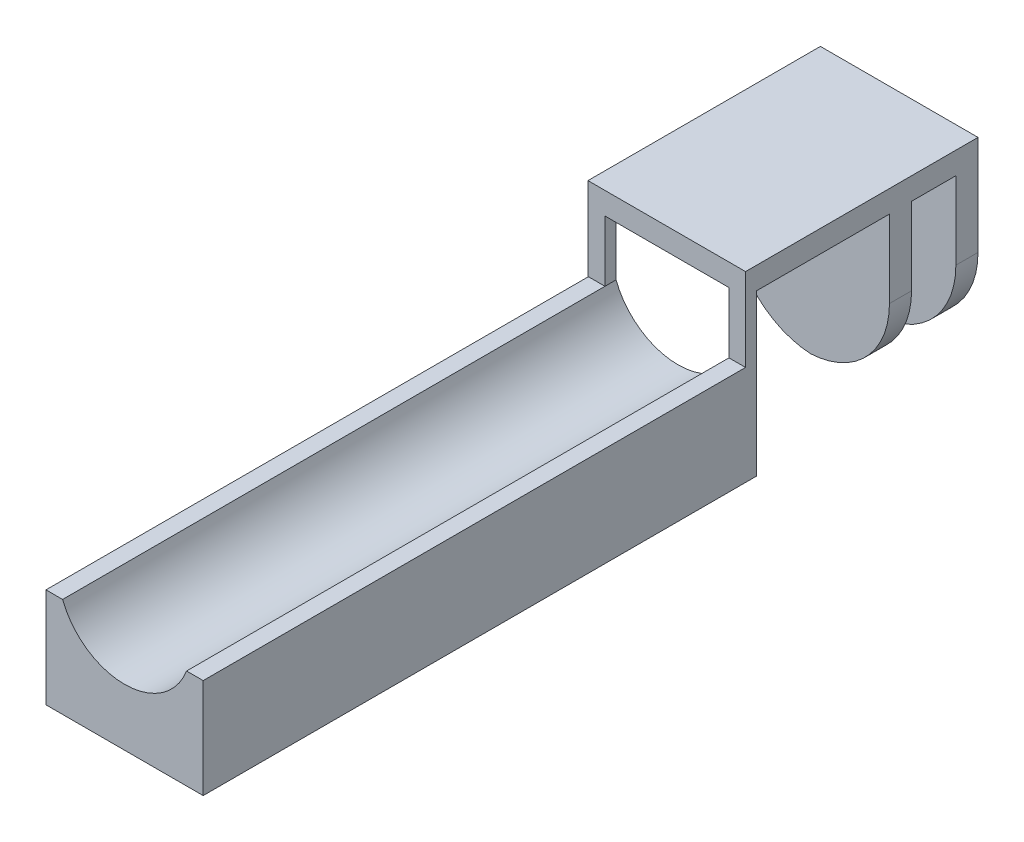
SolidWorks part; units mm, degrees
ref_plane "Front Plane" through (0, 0, 0) normal (0, 0, 1) x (1, 0, 0)
ref_plane "Top Plane" through (0, 0, 0) normal (0, 1, 0) x (1, 0, 0)
ref_plane "Right Plane" through (0, 0, 0) normal (1, 0, 0) x (0, 0, -1)
sketch "Sketch1" plane through (0, 0, 0) normal (0, 0, 1) x (1, 0, 0)
  line L0 (-223.9969, 0) -> (-253.9969, 0)
  line L1 (-253.9969, 0) -> (-253.9969, -180)
  line L2 (-253.9969, -180) -> (30, -180)
  line L3 (30, -180) -> (30, 0)
  line L4 (30, 0) -> (0, 0)
  line L5 (-111.9984, -180) -> (-111.9984, -67.8833) construction
  arc A0 (0, 0) -> (-223.9969, 0) centre (-111.9984, 43.0854) cw
  dimension "D1" = 120
  dimension "D2" = 30
  dimension "D3" = 180
extrude "Boss-Extrude1" add sketch "Sketch1" along normal blind 1000
sketch "Sketch2" plane through (0, 0, 0) normal (0, 0, -1) x (-1, 0, 0)
  line L1 (-30, 0) -> (0, 0)
  line L2 (-30, 0) -> (-30, 150)
  line L3 (-30, 150) -> (0, 150)
  line L4 (0, 0) -> (0, 110)
  line L5 (223.9969, 0) -> (254.7678, 0)
  line L6 (223.9969, 0) -> (223.9969, 110)
  line L7 (223.9969, 150) -> (254.7678, 150)
  line L8 (254.7678, 0) -> (254.7678, 150)
  line L9 (-30, 150) -> (254.7678, 150)
  line L10 (-30, 150) -> (-30, 110)
  line L11 (0, 110) -> (223.9969, 110)
  line L12 (254.7678, 150) -> (254.7678, 110)
  line M5 (0, 0) -> (-30, 0)
  line M9 (253.9969, 0) -> (223.9969, 0)
  dimension "D1" = 150
  dimension "D2" = 40
extrude "Boss-Extrude2" add sketch "Sketch2" against normal blind 20 contours L4 L11 L6 L5 L8 L7 L9 L3 L2 M9 M5 region at (26.7814, 55, 0)
sketch "Sketch3" plane through (0, 0, 0) normal (0, 0, -1) x (-1, 0, 0)
  line L0 (254.7678, 0) -> (254.7678, 150) construction
  line L1 (-30, 150) -> (254.7678, 150)
  line L2 (-30, 150) -> (-30, 110)
  line L3 (-30, 110) -> (254.7678, 110)
  line L4 (254.7678, 150) -> (254.7678, 110)
  dimension "D1" = 40
extrude "Boss-Extrude4" add sketch "Sketch3" along normal blind 400
sketch "Sketch4" plane through (0, 110, 0) normal (0, -1, 0) x (1, 0, 0)
  line L0 (30, -400) -> (30, 0) construction
  line L1 (-254.7678, -400) -> (30, -400)
  line L2 (-254.7678, -400) -> (-254.7678, -360)
  line L3 (-254.7678, -360) -> (30, -360)
  line L4 (30, -400) -> (30, -360)
  line L5 (-254.7678, -400) -> (-254.7678, 0) construction
  line L6 (-254.7678, -240) -> (30, -240)
  line L7 (-254.7678, -240) -> (-254.7678, -280)
  line L8 (-254.7678, -280) -> (30, -280)
  line L9 (30, -240) -> (30, -280)
  dimension "D1" = 40
  dimension "D2" = 80
extrude "Boss-Extrude5" add sketch "Sketch4" along normal up to surface (290 mm away) up to face at (-111.9984, -180, 500)
sketch "Sketch7" plane through (0, 0, -400) normal (0, 0, -1) x (-1, 0, 0)
  circle A0 centre (111.9984, 43.0854) radius 12
  dimension "D1" = 24
extrude "Cut-Extrude1" cut sketch "Sketch7" against normal blind 372
fillet "Fillet1" radius 150 4 edges at (-254.7678, -180, -380) (30, -180, -380) (-254.7678, -180, -260) (30, -180, -260)
